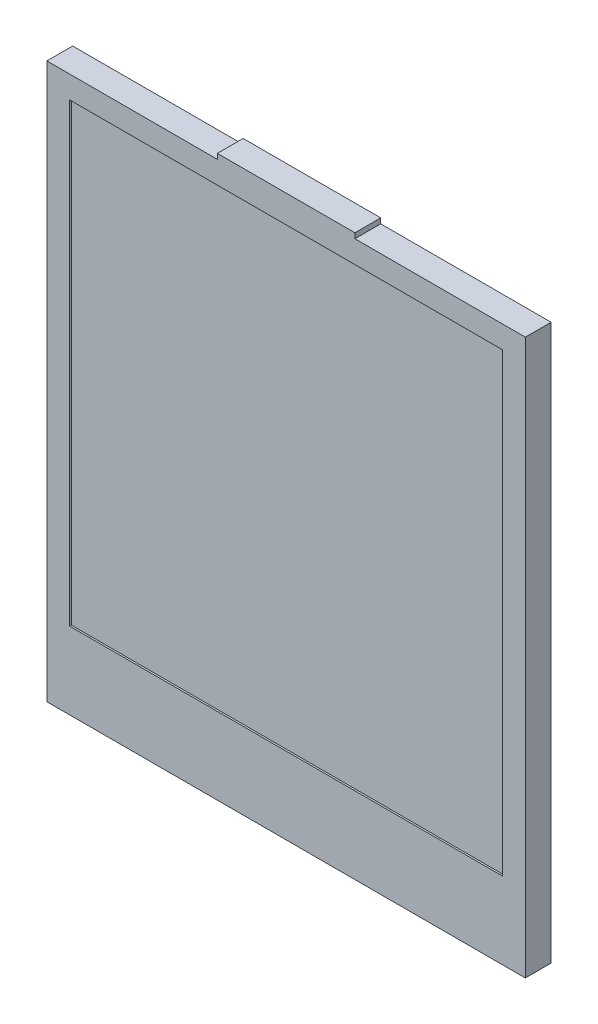
SolidWorks part; units mm, degrees
ref_plane "Front Plane" through (0, 0, 0) normal (0, 0, 1) x (1, 0, 0)
ref_plane "Top Plane" through (0, 0, 0) normal (0, 1, 0) x (1, 0, 0)
ref_plane "Right Plane" through (0, 0, 0) normal (1, 0, 0) x (0, 0, -1)
sketch "Sketch1" plane through (0, 0, 0) normal (0, 0, 1) x (1, 0, 0)
  line L0 (4, 14.55) -> (13.91, 14.55)
  line L1 (-12.585, -13.25) -> (12.585, -13.25)
  line L2 (-12.585, -13.25) -> (-12.585, 13.25)
  line L3 (-12.585, 13.25) -> (12.585, 13.25)
  line L4 (12.585, -13.25) -> (12.585, 13.25)
  line L5 (-12.585, -13.25) -> (12.585, 13.25) construction
  line L6 (-12.585, 13.25) -> (12.585, -13.25) construction
  line L7 (-13.91, -17.72) -> (13.91, -17.72)
  line L8 (-13.91, -17.72) -> (-13.91, 14.55)
  line L9 (-13.91, 14.55) -> (-4, 14.55)
  line L10 (13.91, -17.72) -> (13.91, 14.55)
  line L11 (-13.91, -17.72) -> (13.91, 14.55) construction
  line L12 (-13.91, 14.55) -> (13.91, -17.72) construction
  line L13 (-4, 14.85) -> (4, 14.85)
  line L14 (-4, 14.85) -> (-4, 14.55)
  line L16 (4, 14.85) -> (4, 14.55)
  line L17 (-4, 14.85) -> (4, 14.55) construction
  line L18 (-4, 14.55) -> (4, 14.85) construction
  point P0 (0, 0)
  point P6 (0, -1.585)
  point P12 (0, 14.7)
  dimension "D1" = 26.5
  dimension "D2" = 25.17
  dimension "D3" = 1.3
  dimension "D4" = 27.82
  dimension "D5" = 32.27
  dimension "D6" = 8
  dimension "D7" = 0.3
extrude "Boss-Extrude3" add sketch "Sketch1" along normal blind 1.5
extrude "Boss-Extrude4" add sketch "Sketch1<4>" along normal offset from surface (1.4 mm away) 0.1 separate body contours L2 L3 L4 L1 up to face at (0, 6.5575, 1.5)
sketch "Sketch1<4>" plane through (0, 0, 0) normal (0, 0, 1) x (1, 0, 0) same geometry as "Sketch1"
